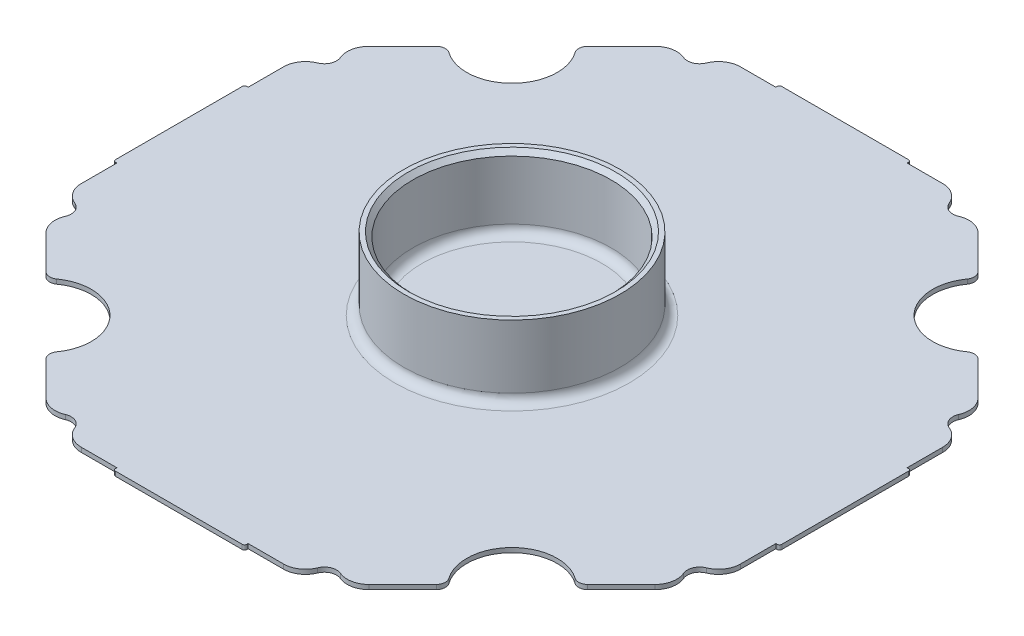
SolidWorks part; units mm, degrees
note: '?' marks a value the reader was unsure of.
ref_plane "Front Plane" through (0, 0, 0) normal (0, 0, 1) x (1, 0, 0)
ref_plane "Top Plane" through (0, 0, 0) normal (0, 1, 0) x (1, 0, 0)
ref_plane "Right Plane" through (0, 0, 0) normal (1, 0, 0) x (0, 0, -1)
sketch "Sketch4" plane through (0, 0, 0) normal (0, 1, 0) x (1, 0, 0)
  line L0 (72.8, -27.5256) -> (72.8, 27.5256)
  line L1 (-73, 28.1665) -> (-73, -28.1665) construction
  line L2 (-71.5355, -31.7021) -> (-31.7021, -71.5355) construction
  line L3 (-28.1665, -73) -> (28.1665, -73) construction
  line L4 (31.7021, -71.5355) -> (71.5355, -31.7021) construction
  line L5 (73, -28.1665) -> (73, 28.1665) construction
  line L6 (71.5355, 31.7021) -> (31.7021, 71.5355) construction
  line L7 (28.1665, 73) -> (-28.1665, 73) construction
  line L8 (-31.7021, 71.5355) -> (-71.5355, 31.7021) construction
  line L9 (-70.9409, -32.0138) -> (-32.0138, -70.9409)
  line L10 (-27.5256, -72.8) -> (27.5256, -72.8)
  line L11 (32.0138, -70.9409) -> (70.9409, -32.0138)
  line L13 (70.9409, 32.0138) -> (32.0138, 70.9409)
  line L14 (27.5256, 72.8) -> (-27.5256, 72.8)
  line L15 (-32.0138, 70.9409) -> (-70.9409, 32.0138)
  line L16 (-72.8, 27.5256) -> (-72.8, -27.5256)
  line L17 (72.8, -30.1547) -> (72.8, -29.5665) [skipped]
  circle A0 centre (0, 0) radius 73 construction
  circle A1 centre (0, 0) radius 72.8 construction
  arc A2 (73, 28.1665) -> (71.5355, 31.7021) centre (68, 28.1665) ccw construction
  arc A3 (71.5355, -31.7021) -> (73, -28.1665) centre (68, -28.1665) ccw construction
  arc A4 (28.1665, -73) -> (31.7021, -71.5355) centre (28.1665, -68) ccw construction
  arc A5 (-31.7021, -71.5355) -> (-28.1665, -73) centre (-28.1665, -68) ccw construction
  arc A6 (-73, -28.1665) -> (-71.5355, -31.7021) centre (-68, -28.1665) ccw construction
  arc A7 (-73, 28.1665) -> (-71.5355, 31.7021) centre (-68, 28.1665) cw construction
  arc A8 (31.7021, 71.5355) -> (28.1665, 73) centre (28.1665, 68) ccw construction
  arc A9 (-28.1665, 73) -> (-31.7021, 71.5355) centre (-28.1665, 68) ccw construction
  circle A13 centre (29.3186, -70.7813) radius 2.5 construction
  circle A15 centre (-29.3186, -70.7813) radius 2.5 construction
  circle A16 centre (-70.7813, -29.3186) radius 2.5 construction
  circle A17 centre (29.3186, 70.7813) radius 2.5 construction
  circle A23 centre (-29.3186, 70.7813) radius 2.5 construction
  circle A24 centre (-70.7813, 29.3186) radius 2.5 construction
  circle A25 centre (70.7813, 29.3186) radius 2.5 construction
  circle A26 centre (70.7813, -29.3186) radius 2.5 construction
  arc A27 (-32.0138, 70.9409) -> (-27.5256, 72.8) centre (-29.3186, 70.7813) ccw
  arc A28 (27.5256, 72.8) -> (32.0138, 70.9409) centre (29.3186, 70.7813) ccw
  arc A29 (70.9409, 32.0138) -> (72.8, 27.5256) centre (70.7813, 29.3186) ccw
  arc A30 (72.8, -27.5256) -> (70.9409, -32.0138) centre (70.7813, -29.3186) ccw
  arc A31 (32.0138, -70.9409) -> (27.5256, -72.8) centre (29.3186, -70.7813) ccw
  arc A32 (-27.5256, -72.8) -> (-32.0138, -70.9409) centre (-29.3186, -70.7813) ccw
  arc A33 (-70.9409, -32.0138) -> (-72.8, -27.5256) centre (-70.7813, -29.3186) ccw
  arc A34 (-72.8, 27.5256) -> (-70.9409, 32.0138) centre (-70.7813, 29.3186) ccw
  circle A35 centre (-29.3186, 70.7813) radius 2.7 construction
  circle A36 centre (29.3186, 70.7813) radius 2.7 construction
  circle A37 centre (70.7813, 29.3186) radius 2.7 construction
  circle A38 centre (70.7813, -29.3186) radius 2.7 construction
  circle A39 centre (29.3186, -70.7813) radius 2.7 construction
  circle A40 centre (-29.3186, -70.7813) radius 2.7 construction
  circle A41 centre (-70.7813, -29.3186) radius 2.7 construction
  circle A42 centre (-70.7813, 29.3186) radius 2.7 construction
  dimension "D1" = 146
  dimension "D2" = 0.2
  dimension "D3" = 5
  dimension "D4" = 5
  dimension "D5" = 0.2
extrude "Boss-Extrude1" add sketch "Sketch4" along normal blind 1
fillet "Fillet2" radius 4.8 16 edges at (-72.8, 0.5, -27.5256) (-70.9409, 0.5, -32.0138) (-72.8, 0.5, 27.5256) (-70.9409, 0.5, 32.0138) (-27.5256, 0.5, -72.8) (-32.0138, 0.5, -70.9409) (32.0138, 0.5, -70.9409) (27.5256, 0.5, -72.8) (72.8, 0.5, -27.5256) (70.9409, 0.5, -32.0138) (70.9409, 0.5, 32.0138) (72.8, 0.5, 27.5256) (32.0138, 0.5, 70.9409) (27.5256, 0.5, 72.8) (-27.5256, 0.5, 72.8) (-32.0138, 0.5, 70.9409)
sketch "Sketch5" plane through (0, 1, 0) normal (0, 1, 0) x (1, 0, 0)
  line L0 (22.3533, 72.8) -> (-22.3533, 72.8) construction
  line L1 (-14.5, 73.6) -> (14.5, 73.6)
  line L2 (-14.5, 73.6) -> (-14.5, 72.8)
  line L3 (-14.5, 72.8) -> (14.5, 72.8)
  line L4 (14.5, 73.6) -> (14.5, 72.8)
  point P6 (0, 72.8)
  point P7 (0, 72.8)
  dimension "D1" = 0.8
  dimension "D2" = 29
extrude "Boss-Extrude2" add sketch "Sketch5" against normal up to surface (1 mm away) up to face at (0, 0, 0)
ref_axis "Axis1" through (0, 1.05, 0) along (0, -1, 0)?
sketch "Sketch7" plane through (0, 1, 0) normal (0, 1, 0) x (1, 0, 0)
  line L0 (67.2836, 35.6712) -> (35.6712, 67.2836) construction
  line L1 (58.5484, 44.4063) -> (44.4063, 58.5484)
  arc A0 (44.4063, 58.5484) -> (58.5484, 44.4063) centre (51.4774, 51.4774) ccw
  dimension "D1" = 20
extrude "Cut-Extrude1" cut sketch "Sketch7" against normal up to next
pattern_circular "CirPattern1" count 4 over 360 about axis through (0, 0, 0) along (0, 1, 0) of "Boss-Extrude2", "Cut-Extrude1"
sketch "Sketch6" plane through (0, 1, 0) normal (0, 1, 0) x (1, 0, 0)
  circle A0 centre (0, 0) radius 21.9
  circle A1 centre (0, 0) radius 23.9
  dimension "D1" = 43.8
  dimension "D2" = 2
extrude "Boss-Extrude3" add sketch "Sketch6" along normal blind 16
fillet "Fillet6" radius 2 8 edges at (44.4063, 0.5, -58.5484) (58.5484, 0.5, -44.4063) (58.5484, 0.5, 44.4063) (44.4063, 0.5, 58.5484) (-44.4063, 0.5, 58.5484) (-58.5484, 0.5, 44.4063) (-58.5484, 0.5, -44.4063) (-44.4063, 0.5, -58.5484)
chamfer "Chamfer1" distance 1 angle 45 1 edges at (0, 17, 21.9)
fillet "Fillet5" radius 2 2 edges at (0, 1, 21.9) (0, 1, 23.9)
fillet "Fillet7" radius 0.5 8 edges at (14.5, 0.5, 73.6) (-14.5, 0.5, 73.6) (-73.6, 0.5, -14.5) (-73.6, 0.5, 14.5) (73.6, 0.5, 14.5) (73.6, 0.5, -14.5) (14.5, 0.5, -73.6) (-14.5, 0.5, -73.6)
